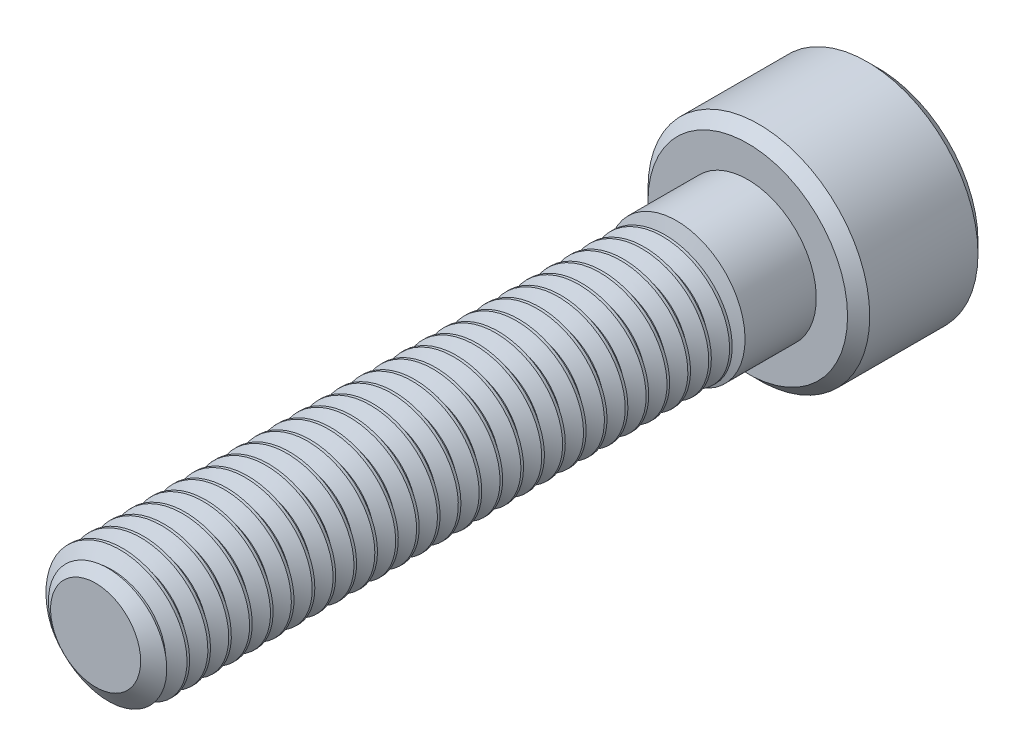
SolidWorks part; units mm, degrees
material "Cast Alloy Steel"
ref_plane "Front Plane" through (0, 0, 0) normal (0, 0, 1) x (1, 0, 0)
ref_plane "Top Plane" through (0, 0, 0) normal (0, 1, 0) x (1, 0, 0)
ref_plane "Right Plane" through (0, 0, 0) normal (1, 0, 0) x (0, 0, -1)
sketch "Sketch1" plane through (0, 0, 0) normal (0, 0, 1) x (1, 0, 0)
  circle A0 centre (0, 0) radius 2.5
  dimension "OD" = 5
extrude "Extrude1" add sketch "Sketch1" against normal blind 25
sketch "Sketch2" plane through (0, 0, 0) normal (0, 0, 1) x (1, 0, 0)
  circle A0 centre (0, 0) radius 2.5 construction
  circle A1 centre (0, 0) radius 2.5
curve "Helix/Spiral1" pitch 0.8 height 25.8 turns 32.25 parameters "pitch"=0.8
sketch "Sketch3" plane through (0, 0, 0) normal (1, 0, 0) x (0, 0, -1)
  line L0 (-0.7, 2.5) -> (-0.4, 1.9804)
  line L1 (-0.4, 1.9804) -> (-0.3, 1.9804)
  line L2 (-0.3, 1.9804) -> (0, 2.5)
  line L3 (-0.7, 2.5) -> (0, 2.5)
  line L4 (-0.35, 2.5) -> (-0.35, 1.9804) construction
  line L5 (-0.55, 2.2402) -> (-0.15, 2.2402) construction
  line L6 (0, 2.5) -> (0, -2.5) construction
  dimension "D1" = 0.1
  dimension "D2" = 0.4
  dimension "D3" = 60
sweep "Cut-Sweep1" cut profiles "Sketch3" path "Helix/Spiral1"
sketch "Sketch4" plane through (0, 0, 0) normal (1, 0, 0) x (0, 0, -1)
  line L0 (0.5417, 2.5) -> (0, 1.7264)
  line L1 (0, 1.7264) -> (0, 2.5)
  line L2 (0.5417, 2.5) -> (0, 2.5)
  line L3 (-0.7, 2.5) -> (0, 2.5) construction
  line L4 (0, 0) -> (7.0209, 0) construction
  dimension "D1" = 55
  dimension "D2" = 0.254
revolve "Cut-Revolve1" cut sketch "Sketch4" angle 360 about L4
sketch "Sketch5" plane through (0, 0, 0) normal (1, 0, 0) x (0, 0, -1)
  line L0 (25, 0) -> (25, 2.3357) construction
  line L1 (25, 2.627) -> (22.2679, 2.627)
  line L2 (25, 2.627) -> (25, 0)
  line L3 (25, 0) -> (22, 0)
  line L4 (22, 1.627) -> (22, 0)
  line L5 (22.2679, 2.627) -> (22, 1.627)
  line L6 (0, 0) -> (22, 0) construction
  point P3 (22, 2.627)
  point P10 (22, 2.627)
  dimension "D1" = 1
  dimension "D2" = 0.127
  dimension "D3" = 15
  dimension "Thread Min" = 22
revolve "partially thread" add sketch "Sketch5" angle 360 about L6
sketch "Sketch6" plane through (0, 0, -25) normal (0, 0, -1) x (-1, 0, 0)
  circle A0 centre (0, 0) radius 4.25
  dimension "head dia" = 8.5
extrude "Extrude2" add sketch "Sketch6" along normal blind 5
sketch "Sketch7" plane through (0, 0, -30) normal (0, 0, -1) x (-1, 0, 0)
  line L1 (0, 2.3094) -> (-2, 1.1547)
  line L2 (-2, 1.1547) -> (-2, -1.1547)
  line L3 (-2, -1.1547) -> (0, -2.3094)
  line L4 (0, -2.3094) -> (2, -1.1547)
  line L5 (2, -1.1547) -> (2, 1.1547)
  line L6 (2, 1.1547) -> (0, 2.3094)
  circle A0 centre (0, 0) radius 2 construction
  dimension "hex dia" = 4
extrude "Cut-Extrude1" cut sketch "Sketch7" against normal blind 3
sketch "Sketch8" plane through (0, 0, -30) normal (0, 0, -1) x (-1, 0, 0)
  circle A0 centre (0, 0) radius 2.3094
extrude "Cut-Extrude2" cut sketch "Sketch8" against normal through all draft 45
chamfer "Chamfer1" distance 0.425 angle 45 2 edges at (-4.25, 0, -30) (-4.25, 0, -25)
sketch "Sketch9" plane through (0, 0, 0) normal (1, 0, 0) x (0, 0, -1)
  line L0 (0, 2.5) -> (0, -2.5) construction
  line L1 (4.4, 2.5) -> (4.4, -2.5) construction
  dimension "D1" = 4.4
equation "\"D3@Helix/Spiral1\" = \"screw length@Extrude1\"+\"pitch@Helix/Spiral1\""
equation "\"D1@Sketch3\" = \"pitch@Helix/Spiral1\"*.125"
equation "\"D2@Sketch3\" = \"pitch@Helix/Spiral1\"*.5"
equation "\"D1@Cut-Extrude1\" = \"hex dia@Sketch7\"*.75"
equation "\"D1@Chamfer1\" = \"head dia@Sketch6\"*.05"
equation "\"D1@Sketch9\" = \"pitch@Helix/Spiral1\"*5.5"
